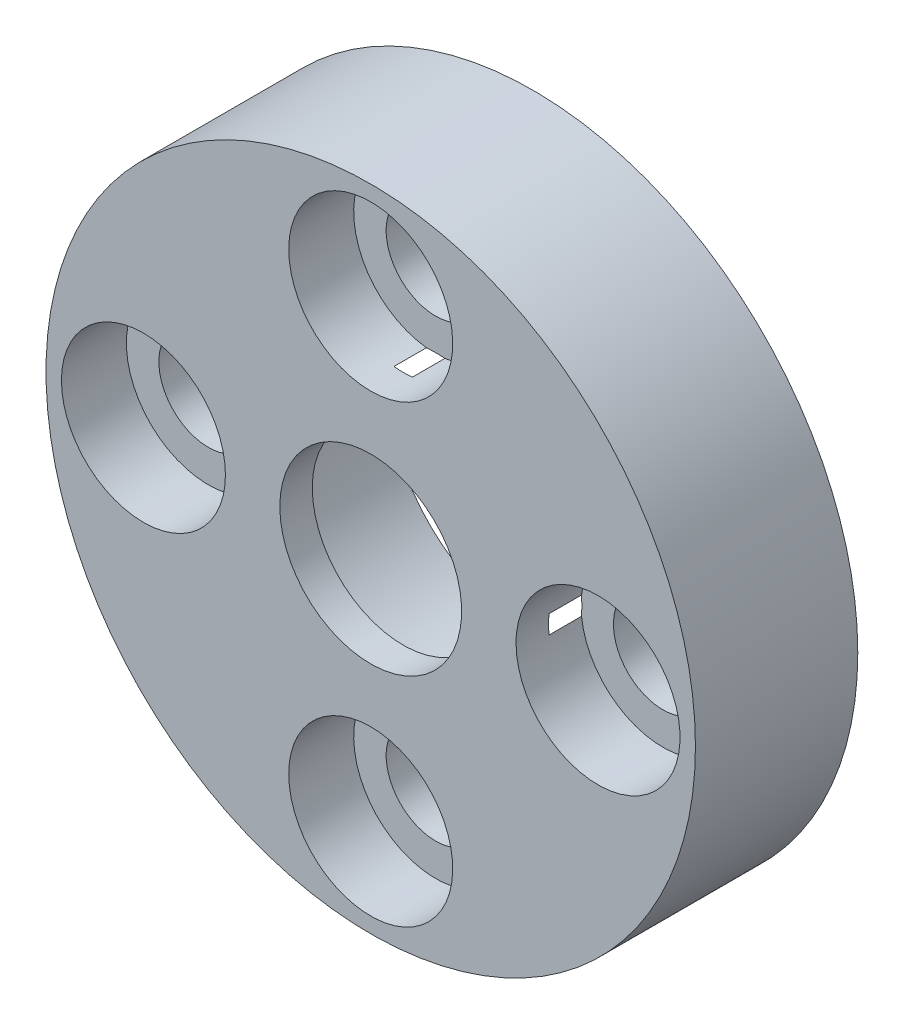
SolidWorks part; units mm, degrees
ref_plane "Front Plane" through (0, 0, 0) normal (0, 0, 1) x (1, 0, 0)
ref_plane "Top Plane" through (0, 0, 0) normal (0, 1, 0) x (1, 0, 0)
ref_plane "Right Plane" through (0, 0, 0) normal (1, 0, 0) x (0, 0, -1)
sketch "Sketch1" plane through (0, 0, 0) normal (0, 0, 1) x (1, 0, 0)
  circle A0 centre (0, 0) radius 10 construction
  circle A1 centre (-7, 0) radius 1.525
  circle A2 centre (-7, 0) radius 1.525
  circle A3 centre (0, -7) radius 1.525
  circle A4 centre (0, -7) radius 1.525
  circle A5 centre (7, 0) radius 1.525
  circle A6 centre (7, 0) radius 1.525
  circle A7 centre (0, 7) radius 1.525
  circle A8 centre (0, 7) radius 1.525
  circle A9 centre (0, 0) radius 10
  dimension "D1" = 0
  dimension "D2" = 0
  dimension "D3" = 0
  dimension "D4" = 0
extrude "Boss-Extrude1" add sketch "Sketch1" along normal blind 5
sketch "Sketch2" plane through (0, 0, 0) normal (0, 0, -1) x (-1, 0, 0)
  circle A1 centre (0, 0) radius 4.5
  dimension "D1" = 9
extrude "Cut-Extrude1" cut sketch "Sketch2" against normal offset from surface (4 mm away) 1 up to face at (8.525, 0, 5)
sketch "Sketch3" plane through (0, 0, 4) normal (0, 0, -1) x (-1, 0, 0)
  circle A0 centre (0, 0) radius 2.8
  dimension "D1" = 5.6
extrude "Cut-Extrude2" cut sketch "Sketch3" against normal through all
sketch "Sketch5" plane through (0, 0, 5) normal (0, 0, -1) x (-1, 0, 0)
  circle A0 centre (7, 0) radius 1.525 construction
  circle A1 centre (0, -7) radius 1.525 construction
  circle A2 centre (-7, 0) radius 1.525 construction
  circle A3 centre (0, 7) radius 1.525 construction
  circle A4 centre (7, 0) radius 1.525
  circle A5 centre (0, -7) radius 1.525
  circle A6 centre (-7, 0) radius 1.525
  circle A7 centre (0, 7) radius 1.525
  circle A8 centre (7, 0) radius 2.525
  circle A9 centre (0, -7) radius 2.525
  circle A10 centre (-7, 0) radius 2.525
  circle A11 centre (0, 7) radius 2.525
  dimension "D1" = 1
extrude "Cut-Extrude4" cut sketch "Sketch5" along normal offset from surface (2 mm away) 3 up to face at (-4.5, 0, 0)
